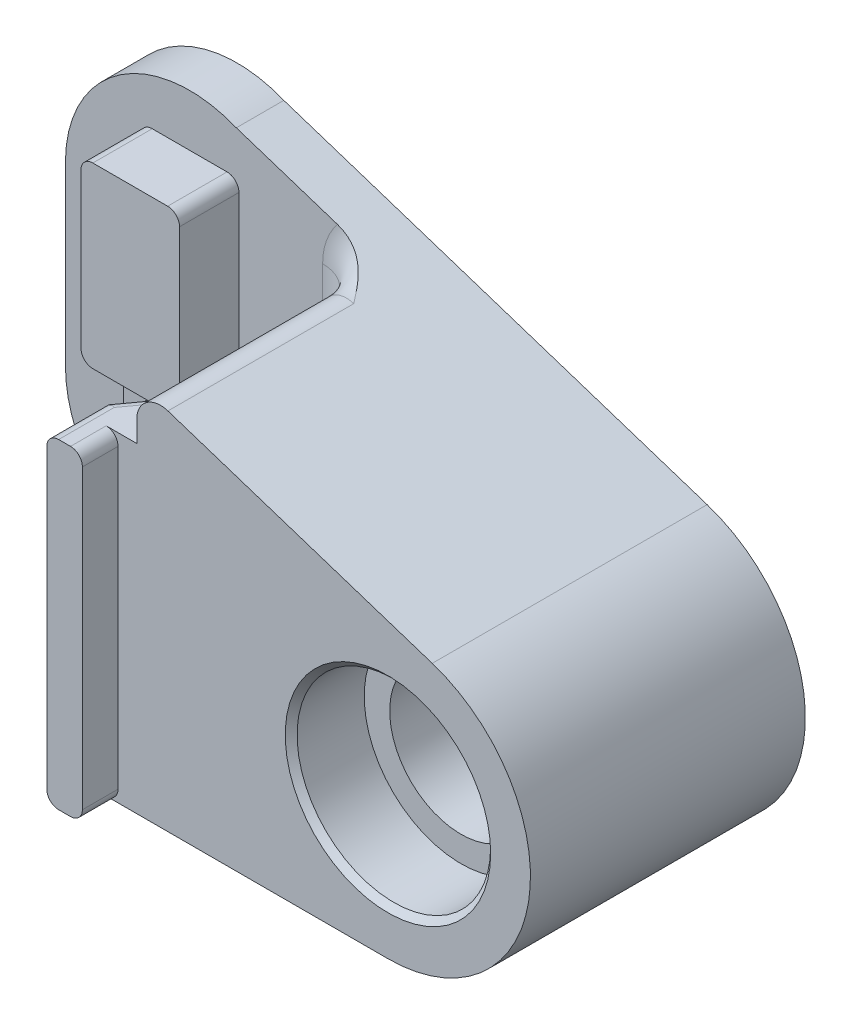
SolidWorks part; units mm, degrees
note: The reader was unsure of these and kept them because the rebuilt part matched: shared geometry of "Эскиз1<3>", "Эскиз1<4>", "Эскиз1<5>", "Эскиз1<6>", "Эскиз1<7>".
ref_plane "Спереди" through (0, 0, 0) normal (0, 0, 1) x (1, 0, 0)
ref_plane "Сверху" through (0, 0, 0) normal (0, 1, 0) x (1, 0, 0)
ref_plane "Справа" through (0, 0, 0) normal (1, 0, 0) x (0, 0, -1)
sketch "Эскиз1" plane through (0, 0, 0) normal (0, 0, 1) x (1, 0, 0)
  line L1 (-15, 7.3453) -> (-15, -6.2734) construction
  line L2 (-19.15, 7.4915) -> (-10.85, 7.4915)
  line L3 (-19.15, 7.4915) -> (-19.15, -4.5085)
  line L4 (-19.15, -4.5085) -> (-10.85, -4.5085)
  line L5 (-10.85, 7.4915) -> (-10.85, -4.5085)
  line L10 (20.85, -8.9637) -> (-0.3, -8.9637)
  line L11 (-10.85, 7.4915) -> (-10.85, 22.4915)
  line L12 (-0.3, -8.9637) -> (-0.3, 22.5771)
  line L14 (-19.15, 22.4915) -> (-10.85, 22.4915)
  line L16 (-19.15, 7.4915) -> (-19.15, 22.4915)
  line L17 (-25.4552, 16.5363) -> (-25.4552, 1.4915)
  line L18 (-19.15, 7.4915) -> (-10.85, 7.4915)
  line L19 (-0.3, -8.9637) -> (-15, -8.9637)
  line L20 (24.5794, 14.442) -> (-11.0686, 26.0982)
  circle A0 centre (20.85, 3.0363) radius 9.5
  circle A2 centre (20.85, 3.0363) radius 12
  circle A3 centre (20.85, 3.0363) radius 6
  circle A5 centre (-15, 1.4915) radius 3.25
  circle A6 centre (20.85, 3.0363) radius 8.15
  arc A7 (-15, -8.9637) -> (-25.4552, 1.4915) centre (-15, 1.4915) cw
  arc A8 (-25.4552, 16.5363) -> (-11.0686, 26.0982) centre (-15.0008, 16.4106) cw
  point P5 (-15, 22.4915)
  point P6 (-15, 7.4915)
  dimension "D1" = 8.3
  dimension "D2" = 24
  dimension "D3" = 12
  dimension "D4" = 19
  dimension "D5" = 16.3
  dimension "D8" = 15
  dimension "D6" = 6
  dimension "D7" = 10.4552
  dimension "D9" = 6
  dimension "D10" = 14.7
  dimension "D11" = 21.15
extrude "Бобышка-Вытянуть1" add sketch "Эскиз1" along normal blind 4
extrude "Бобышка-Вытянуть2" add sketch "Эскиз1<3>" along normal blind 23.15 contours L10 A2 L20 L12 | A2 A6 | A0 A6
sketch "Эскиз1<3>" plane through (0, 0, 0) normal (0, 0, 1) x (1, 0, 0) same geometry as "Эскиз1"
extrude "Бобышка-Вытянуть3" add sketch "Эскиз1<4>" along normal blind 8 from offset 9 contours A6 A3
sketch "Эскиз1<4>" plane through (0, 0, 0) normal (0, 0, 1) x (1, 0, 0) same geometry as "Эскиз1"
extrude "Бобышка-Вытянуть4" add sketch "Эскиз1<5>" along normal blind 9 contours L18 L11 L14 L16
sketch "Эскиз1<5>" plane through (0, 0, 0) normal (0, 0, 1) x (1, 0, 0) same geometry as "Эскиз1"
fillet "Скругление1" radius 2 1 edges at (-0.3, 22.5771, 13.575)
sketch "Эскиз4" plane through (0, -8.9637, 0) normal (0, -1, 0) x (1, 0, 0)
  line L0 (-11.0922, 19) -> (15.822, 19) construction
  line L1 (-0.3, 4) -> (-15, 4) construction
  line L2 (-4.88, 26.15) -> (-4.88, 21.15)
  line L3 (-4.88, 21.15) -> (-0.3, 14.85)
  line L4 (20.85, 0) -> (-15, 0) construction
  line L5 (-1.88, 23.15) -> (-0.3, 23.15)
  line L10 (-0.3, 12.9089) -> (-0.3, 30.6625) construction
  line L13 (-4.88, 26.15) -> (-1.88, 26.15)
  line L14 (-1.88, 23.15) -> (-1.88, 26.15)
  line L15 (-0.3, 23.15) -> (-0.3, 4) construction
  line L16 (-0.3, 14.85) -> (-0.3, 23.15)
  point P4 (-0.3, 19)
  dimension "D1" = 15
  dimension "D2" = 1.58
  dimension "D3" = 8.3
  dimension "D4" = 3
  dimension "D5" = 3
  dimension "D6" = 5
  dimension "D7" = 4.15
  dimension "D8" = 23.15
extrude "Бобышка-Вытянуть5" add sketch "Эскиз4" against normal blind 27
fillet "Скругление2" radius 1 7 edges at (-1.88, -8.9637, 24.65) (-1.88, 18.0363, 24.65) (-0.3, -8.9637, 9.425) (-4.88, 18.0363, 23.65) (-2.59, 18.0363, 18) (-2.59, -8.9637, 18) (-4.88, -8.9637, 23.65)
extrude "Вырез-Вытянуть1" cut sketch "Эскиз1<6>" along normal blind 2 contours A0 A6
sketch "Эскиз1<6>" plane through (0, 0, 0) normal (0, 0, 1) x (1, 0, 0) same geometry as "Эскиз1"
chamfer "Фаска1" distance 2.3 angle 45 1 edges at (26.85, 3.0363, 9)
chamfer "Фаска2" distance 1.3 angle 45 1 edges at (29, 3.0363, 2)
fillet "Скругление4" radius 3.5 3 edges at (0.5259, 21.4381, 4) (-0.0071, -8.6708, 4) (-0.3, 5.9276, 4)
extrude "Бобышка-Вытянуть6" add sketch "Эскиз1<7>" along normal blind 5.4
sketch "Эскиз1<7>" plane through (0, 0, 0) normal (0, 0, 1) x (1, 0, 0) same geometry as "Эскиз1"
fillet "Скругление3" radius 1 6 edges at (-10.85, 7.4915, 7.2) (-10.85, 22.4915, 6.5) (-19.15, 22.4915, 6.5) (-19.15, 7.4915, 7.2) (-10.85, -4.5085, 4.7) (-19.15, -4.5085, 4.7)
chamfer "Фаска3" distance 0.5 angle 45 2 edges at (29, 3.0363, 23.15) (30.35, 3.0363, 0)
